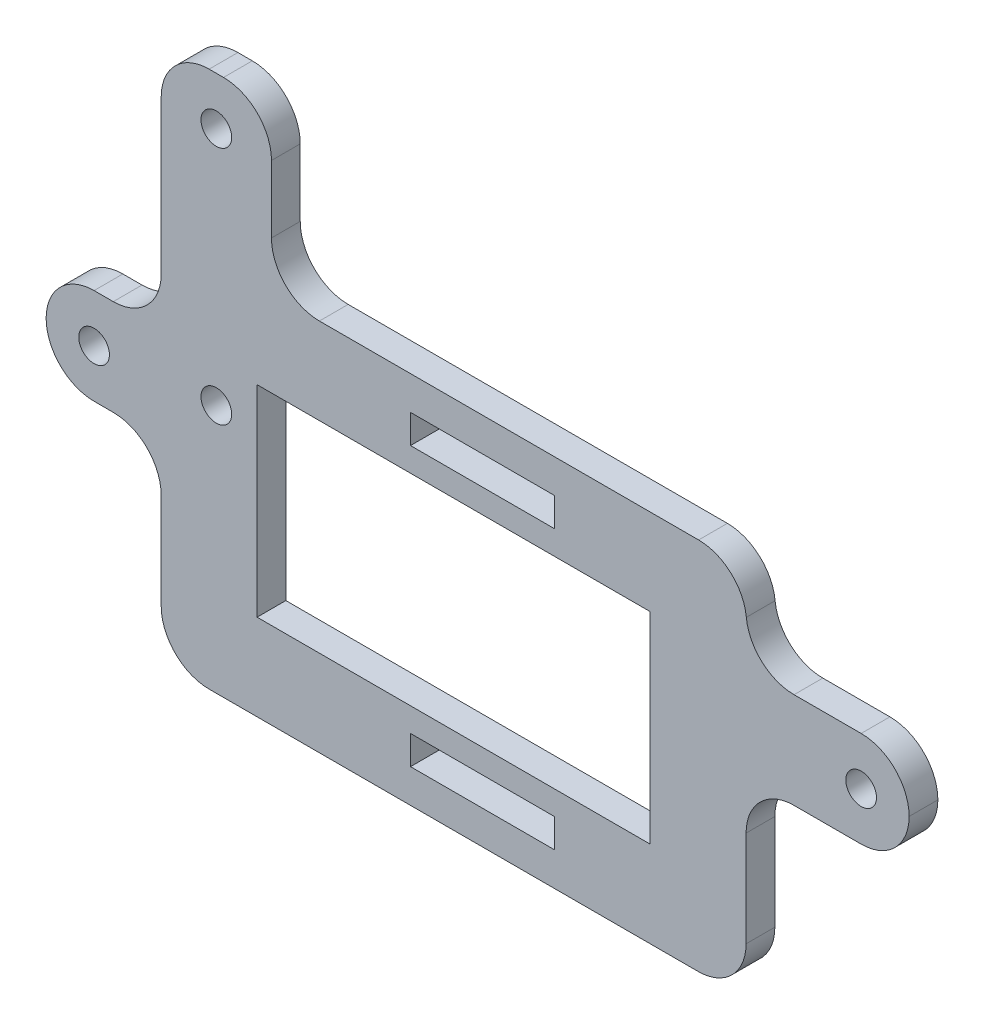
SolidWorks part; units mm, degrees
ref_plane "Plano frontal" through (0, 0, 0) normal (0, 0, 1) x (1, 0, 0)
ref_plane "Plano superior" through (0, 0, 0) normal (0, 1, 0) x (1, 0, 0)
ref_plane "Plano direito" through (0, 0, 0) normal (1, 0, 0) x (0, 0, -1)
sketch "Esboço1" plane through (0, 0, 0) normal (0, 0, 1) x (1, 0, 0)
  line L0 (0, 0) -> (30.5, 0) construction
  line L1 (-30.5, -19.5) -> (30.5, -19.5)
  line L2 (-30.5, -19.5) -> (-30.5, 19.5)
  line L3 (-30.5, 19.5) -> (30.5, 19.5)
  line L4 (30.5, -19.5) -> (30.5, 19.5)
  line L5 (-30.5, -19.5) -> (30.5, 19.5) construction
  line L6 (-30.5, 19.5) -> (30.5, -19.5) construction
  line L7 (-20.5, -10.5) -> (20.5, -10.5)
  line L8 (-20.5, -10.5) -> (-20.5, 10.5)
  line L9 (-20.5, 10.5) -> (20.5, 10.5)
  line L10 (20.5, -10.5) -> (20.5, 10.5)
  line L11 (-20.5, -10.5) -> (20.5, 10.5) construction
  line L12 (-20.5, 10.5) -> (20.5, -10.5) construction
  line L13 (0, 0) -> (0, 19.5) construction
  line L14 (-20.5, 0) -> (-30.5, 0) construction
  line L19 (-4.5, -16) -> (10.5, -16)
  line L25 (10.5, -13) -> (10.5, -16)
  line L34 (-19, 36.5) -> (-30.5, 36.5)
  line L35 (-19, 36.5) -> (-19, 19.5)
  line L36 (-19, 19.5) -> (-30.5, 19.5)
  line L37 (-30.5, 36.5) -> (-30.5, 19.5)
  line L38 (-19, 36.5) -> (-30.5, 19.5) construction
  line L39 (-19, 19.5) -> (-30.5, 36.5) construction
  line L40 (-4.5, 13) -> (10.5, 13)
  line L41 (-4.5, 13) -> (-4.5, 16)
  line L42 (-4.5, 16) -> (10.5, 16)
  line L43 (10.5, 13) -> (10.5, 16)
  line L44 (-4.5, 13) -> (10.5, 16) construction
  line L45 (-4.5, 16) -> (10.5, 13) construction
  line L46 (-4.5, -13) -> (10.5, -13)
  line L47 (-4.5, -13) -> (-4.5, -16)
  line L48 (-42.5, 10.5) -> (-30.5, 10.5)
  line L49 (-42.5, 0.5) -> (-30.5, 0.5)
  line L50 (-42.5, 0.5) -> (-42.5, 19.5)
  line L51 (-42.5, 19.5) -> (-30.5, 19.5)
  line L52 (-30.5, 0.5) -> (-30.5, 19.5)
  line L53 (-42.5, 0.5) -> (-30.5, 19.5) construction
  line L54 (-42.5, 19.5) -> (-30.5, 0.5) construction
  line L55 (47.5, 0.5) -> (30.5, 0.5)
  line L56 (47.5, 0.5) -> (47.5, 10.5)
  line L57 (47.5, 10.5) -> (30.5, 10.5)
  circle A5 centre (-24.75, 31.5) radius 1.6
  circle A9 centre (24.75, 5) radius 1.6 construction
  circle A10 centre (24.75, -5) radius 1.6 construction
  circle A11 centre (-24.75, -5) radius 1.6 construction
  circle A12 centre (-24.75, 5) radius 1.6 construction
  circle A13 centre (-24.75, 6.5) radius 1.6
  circle A14 centre (-37.5, 5.5) radius 1.6
  circle A15 centre (-37.5, 14.5) radius 1.6 construction
  circle A16 centre (42.5, 5.5) radius 1.6
  point P0 (0, 0)
  point P6 (0, 0)
  point P13 (3, 14.5)
  point P38 (-36.5, 10)
  point P45 (47.5, 5.5)
  point P57 (-24.75, 28)
  dimension "D5" = 3.2
  dimension "D8" = 15
  dimension "D10" = 25
  dimension "D12" = 7
  dimension "D17" = 20
  dimension "D1" = 41
  dimension "D2" = 21
  dimension "D3" = 9
  dimension "D4" = 10
  dimension "D6" = 49.5
  dimension "D7" = 10
  dimension "D9" = 5
  dimension "D11" = 3
  dimension "D13" = 5
  dimension "D14" = 5
  dimension "D15" = 12
  dimension "D16" = 5
  dimension "D19" = 5
  dimension "D20" = 5
  dimension "D21" = 5
  dimension "D22" = 12
extrude "Ressalto-extrusão1" add sketch "Esboço1" along normal blind 3
fillet "Filete1" radius 5 13 edges at (-19, 36.5, 1.5) (-30.5, 36.5, 1.5) (30.5, -19.5, 1.5) (-30.5, -19.5, 1.5) (-42.5, 0.5, 1.5) (-19, 19.5, 1.5) (-30.5, 0.5, 1.5) (-30.5, 10.5, 1.5) (-42.5, 10.5, 1.5) (30.5, 0.5, 1.5) (47.5, 0.5, 1.5) (47.5, 10.5, 1.5) (30.5, 10.5, 1.5)
fillet "Filete4" radius 5 1 edges at (30.5, 19.5, 1.5)
